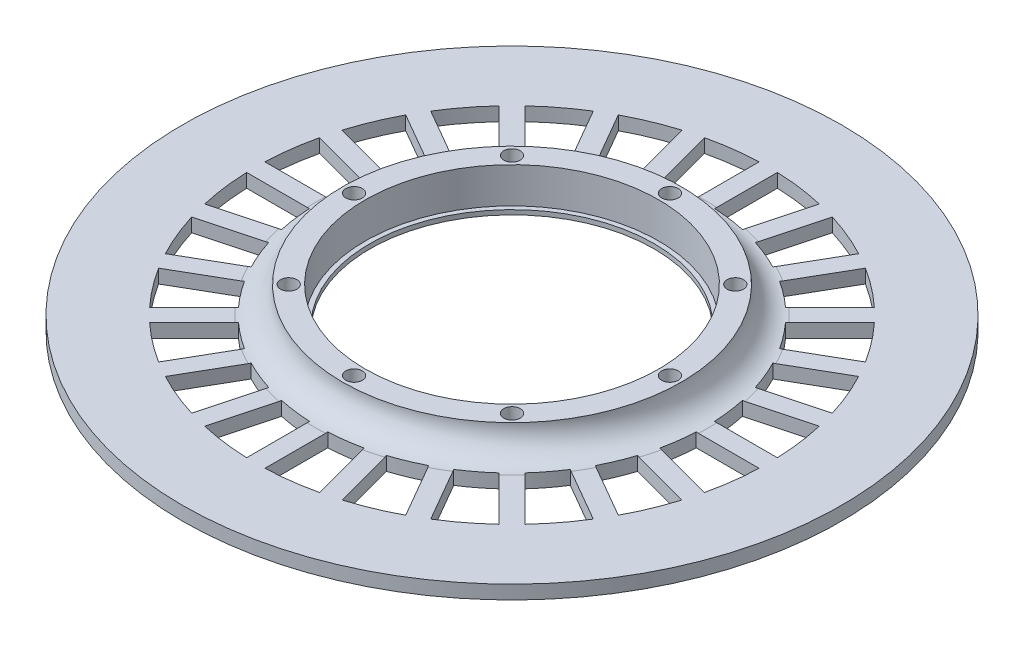
SolidWorks part; units mm, degrees
ref_plane "Front Plane" through (0, 0, 0) normal (0, 0, 1) x (1, 0, 0)
ref_plane "Top Plane" through (0, 0, 0) normal (0, 1, 0) x (1, 0, 0)
ref_plane "Right Plane" through (0, 0, 0) normal (1, 0, 0) x (0, 0, -1)
sketch "Sketch1" plane through (0, 0, 0) normal (0, 1, 0) x (1, 0, 0)
  circle A0 centre (0, 0) radius 16.025
  circle A1 centre (0, 0) radius 36
  dimension "D1" = 32.05
  dimension "D2" = 72
extrude "Boss-Extrude1" add sketch "Sketch1" along normal blind 1
sketch "Sketch2" plane through (0, 0, 0) normal (0, -1, 0) x (1, 0, 0)
  circle A0 centre (0, 0) radius 17.25 construction
  circle A1 centre (0, 0) radius 18.5 construction
  circle A2 centre (0, 0) radius 18.5
  circle A3 centre (0, 0) radius 16.025 construction
  circle A4 centre (0, 0) radius 16.025
  arc A5 (-1.2, 18.461) -> (-12.2054, 13.9025) centre (0, 0) ccw construction
  point P3 (0, -17.25)
  point P11 (0, 0)
  point P15 (0, 17.3144)
  point P16 (0, 0)
  point P17 (-5.6457, -16.7382)
  point P18 (0, 0)
extrude "Boss-Extrude2" add sketch "Sketch2" against normal offset from surface (3.9 mm away) 3.9 up to face at (0, 0, 36)
fillet "Fillet1" radius 2.9 1 edges at (0, 1, 18.5)
sketch "Sketch4" plane through (0, 0, 0) normal (0, 1, 0) x (1, 0, 0)
  circle A0 centre (0, 0) radius 15.525
  circle A1 centre (0, 0) radius 36
  circle A2 centre (0, 0) radius 36
  circle A3 centre (0, 0) radius 16.025 construction
  dimension "D2" = 0.5
  dimension "D1" = 0
extrude "Boss-Extrude3" add sketch "Sketch4" against normal blind 0.5
sketch "Sketch5" plane through (0, 1, 0) normal (0, 1, 0) x (1, 0, 0)
  line L0 (27.99, -0.75) -> (19.9859, -0.75) construction
  line L1 (19.9859, 0.75) -> (27.99, 0.75) construction
  line L2 (27.99, -0.75) -> (19.9859, -0.75) construction
  line L3 (19.9859, 0.75) -> (27.99, 0.75) construction
  line L4 (0, 0) -> (36, 0) construction
  line L5 (0, 0) -> (34.7733, 9.3175) construction
  line L6 (34.7733, 9.3175) -> (36, 0) construction
  line L7 (0, 0) -> (35.3867, 4.6587) construction
  line L8 (27.99, 1) -> (21.1263, 1)
  line L9 (27.295, 6.2784) -> (20.6653, 4.502)
  line L10 (27.99, -1) -> (21.1263, -1)
  line L11 (27.295, -6.2784) -> (20.6653, -4.502)
  line L12 (26.7774, -8.2103) -> (20.1477, -6.4338)
  line L13 (24.74, -13.129) -> (18.796, -9.6971)
  line L14 (23.74, -14.861) -> (17.796, -11.4292)
  line L15 (20.499, -19.0848) -> (15.6457, -14.2315)
  line L16 (19.0848, -20.499) -> (14.2315, -15.6457)
  line L17 (14.861, -23.74) -> (11.4292, -17.796)
  line L18 (13.129, -24.74) -> (9.6971, -18.796)
  line L19 (8.2103, -26.7774) -> (6.4338, -20.1477)
  line L20 (6.2784, -27.295) -> (4.502, -20.6653)
  line L21 (1, -27.99) -> (1, -21.1263)
  line L22 (-1, -27.99) -> (-1, -21.1263)
  line L23 (-6.2784, -27.295) -> (-4.502, -20.6653)
  line L24 (-8.2103, -26.7774) -> (-6.4338, -20.1477)
  line L25 (-13.129, -24.74) -> (-9.6971, -18.796)
  line L26 (-14.861, -23.74) -> (-11.4292, -17.796)
  line L27 (-19.0848, -20.499) -> (-14.2315, -15.6457)
  line L28 (-20.499, -19.0848) -> (-15.6457, -14.2315)
  line L29 (-23.74, -14.861) -> (-17.796, -11.4292)
  line L30 (-24.74, -13.129) -> (-18.796, -9.6971)
  line L31 (-26.7774, -8.2103) -> (-20.1477, -6.4338)
  line L32 (-27.295, -6.2784) -> (-20.6653, -4.502)
  line L33 (-27.99, -1) -> (-21.1263, -1)
  line L34 (-27.99, 1) -> (-21.1263, 1)
  line L35 (-27.295, 6.2784) -> (-20.6653, 4.502)
  line L36 (-26.7774, 8.2103) -> (-20.1477, 6.4338)
  line L37 (-24.74, 13.129) -> (-18.796, 9.6971)
  line L38 (-23.74, 14.861) -> (-17.796, 11.4292)
  line L39 (-20.499, 19.0848) -> (-15.6457, 14.2315)
  line L40 (-19.0848, 20.499) -> (-14.2315, 15.6457)
  line L41 (-14.861, 23.74) -> (-11.4292, 17.796)
  line L42 (-13.129, 24.74) -> (-9.6971, 18.796)
  line L43 (-8.2103, 26.7774) -> (-6.4338, 20.1477)
  line L44 (-6.2784, 27.295) -> (-4.502, 20.6653)
  line L45 (-1, 27.99) -> (-1, 21.1263)
  line L46 (1, 27.99) -> (1, 21.1263)
  line L47 (6.2784, 27.295) -> (4.502, 20.6653)
  line L48 (8.2103, 26.7774) -> (6.4338, 20.1477)
  line L49 (13.129, 24.74) -> (9.6971, 18.796)
  line L50 (14.861, 23.74) -> (11.4292, 17.796)
  line L51 (19.0848, 20.499) -> (14.2315, 15.6457)
  line L52 (20.499, 19.0848) -> (15.6457, 14.2315)
  line L53 (23.74, 14.861) -> (17.796, 11.4292)
  line L54 (24.74, 13.129) -> (18.796, 9.6971)
  line L55 (26.7774, 8.2103) -> (20.1477, 6.4338)
  line L56 (0, 0) -> (21.1263, 1) construction
  circle A0 centre (0, 0) radius 21.15 construction
  circle A2 centre (0, 0) radius 36 construction
  arc A3 (21.1263, 1) -> (20.6653, 4.502) centre (0, 0) ccw
  arc A4 (27.99, 1) -> (27.295, 6.2784) centre (0, 0) ccw
  arc A5 (27.295, -6.2784) -> (27.99, -1) centre (0, 0) ccw
  arc A6 (20.6653, -4.502) -> (21.1263, -1) centre (0, 0) ccw
  arc A7 (24.74, -13.129) -> (26.7774, -8.2103) centre (0, 0) ccw
  arc A8 (18.796, -9.6971) -> (20.1477, -6.4338) centre (0, 0) ccw
  arc A9 (20.499, -19.0848) -> (23.74, -14.861) centre (0, 0) ccw
  arc A10 (15.6457, -14.2315) -> (17.796, -11.4292) centre (0, 0) ccw
  arc A11 (14.861, -23.74) -> (19.0848, -20.499) centre (0, 0) ccw
  arc A12 (11.4292, -17.796) -> (14.2315, -15.6457) centre (0, 0) ccw
  arc A13 (8.2103, -26.7774) -> (13.129, -24.74) centre (0, 0) ccw
  arc A14 (6.4338, -20.1477) -> (9.6971, -18.796) centre (0, 0) ccw
  arc A15 (1, -27.99) -> (6.2784, -27.295) centre (0, 0) ccw
  arc A16 (1, -21.1263) -> (4.502, -20.6653) centre (0, 0) ccw
  arc A17 (-6.2784, -27.295) -> (-1, -27.99) centre (0, 0) ccw
  arc A18 (-4.502, -20.6653) -> (-1, -21.1263) centre (0, 0) ccw
  arc A19 (-13.129, -24.74) -> (-8.2103, -26.7774) centre (0, 0) ccw
  arc A20 (-9.6971, -18.796) -> (-6.4338, -20.1477) centre (0, 0) ccw
  arc A21 (-19.0848, -20.499) -> (-14.861, -23.74) centre (0, 0) ccw
  arc A22 (-14.2315, -15.6457) -> (-11.4292, -17.796) centre (0, 0) ccw
  arc A23 (-23.74, -14.861) -> (-20.499, -19.0848) centre (0, 0) ccw
  arc A24 (-17.796, -11.4292) -> (-15.6457, -14.2315) centre (0, 0) ccw
  arc A25 (-26.7774, -8.2103) -> (-24.74, -13.129) centre (0, 0) ccw
  arc A26 (-20.1477, -6.4338) -> (-18.796, -9.6971) centre (0, 0) ccw
  arc A27 (-27.99, -1) -> (-27.295, -6.2784) centre (0, 0) ccw
  arc A28 (-21.1263, -1) -> (-20.6653, -4.502) centre (0, 0) ccw
  arc A29 (-27.295, 6.2784) -> (-27.99, 1) centre (0, 0) ccw
  arc A30 (-20.6653, 4.502) -> (-21.1263, 1) centre (0, 0) ccw
  arc A31 (-24.74, 13.129) -> (-26.7774, 8.2103) centre (0, 0) ccw
  arc A32 (-18.796, 9.6971) -> (-20.1477, 6.4338) centre (0, 0) ccw
  arc A33 (-20.499, 19.0848) -> (-23.74, 14.861) centre (0, 0) ccw
  arc A34 (-15.6457, 14.2315) -> (-17.796, 11.4292) centre (0, 0) ccw
  arc A35 (-14.861, 23.74) -> (-19.0848, 20.499) centre (0, 0) ccw
  arc A36 (-11.4292, 17.796) -> (-14.2315, 15.6457) centre (0, 0) ccw
  arc A37 (-8.2103, 26.7774) -> (-13.129, 24.74) centre (0, 0) ccw
  arc A38 (-6.4338, 20.1477) -> (-9.6971, 18.796) centre (0, 0) ccw
  arc A39 (-1, 27.99) -> (-6.2784, 27.295) centre (0, 0) ccw
  arc A40 (-1, 21.1263) -> (-4.502, 20.6653) centre (0, 0) ccw
  arc A41 (6.2784, 27.295) -> (1, 27.99) centre (0, 0) ccw
  arc A42 (4.502, 20.6653) -> (1, 21.1263) centre (0, 0) ccw
  arc A43 (13.129, 24.74) -> (8.2103, 26.7774) centre (0, 0) ccw
  arc A44 (9.6971, 18.796) -> (6.4338, 20.1477) centre (0, 0) ccw
  arc A45 (19.0848, 20.499) -> (14.861, 23.74) centre (0, 0) ccw
  arc A46 (14.2315, 15.6457) -> (11.4292, 17.796) centre (0, 0) ccw
  arc A47 (23.74, 14.861) -> (20.499, 19.0848) centre (0, 0) ccw
  arc A48 (17.796, 11.4292) -> (15.6457, 14.2315) centre (0, 0) ccw
  arc A49 (26.7774, 8.2103) -> (24.74, 13.129) centre (0, 0) ccw
  arc A50 (20.1477, 6.4338) -> (18.796, 9.6971) centre (0, 0) ccw
  dimension "D1" = 15
  dimension "D2" = 1
  dimension "D4" = 21.15
  dimension "D3" = 24
extrude "Cut-Extrude1" cut sketch "Sketch5" against normal through all both and the other way through all
sketch "Sketch7" plane through (0, 3.9, 0) normal (0, 1, 0) x (1, 0, 0)
  line L0 (0, 0) -> (0, 17.25) construction
  circle A0 centre (0, 17.25) radius 0.9
  circle A1 centre (12.1976, 12.1976) radius 0.9
  circle A2 centre (17.25, 0) radius 0.9
  circle A3 centre (12.1976, -12.1976) radius 0.9
  circle A4 centre (0, -17.25) radius 0.9
  circle A5 centre (-12.1976, -12.1976) radius 0.9
  circle A6 centre (-17.25, 0) radius 0.9
  circle A7 centre (-12.1976, 12.1976) radius 0.9
  point P5 (0, 0)
  point P6 (0, 0)
  point P21 (0, 0)
  dimension "D1" = 1.8
  dimension "D2" = 8
extrude "Cut-Extrude2" cut sketch "Sketch7" against normal through all
